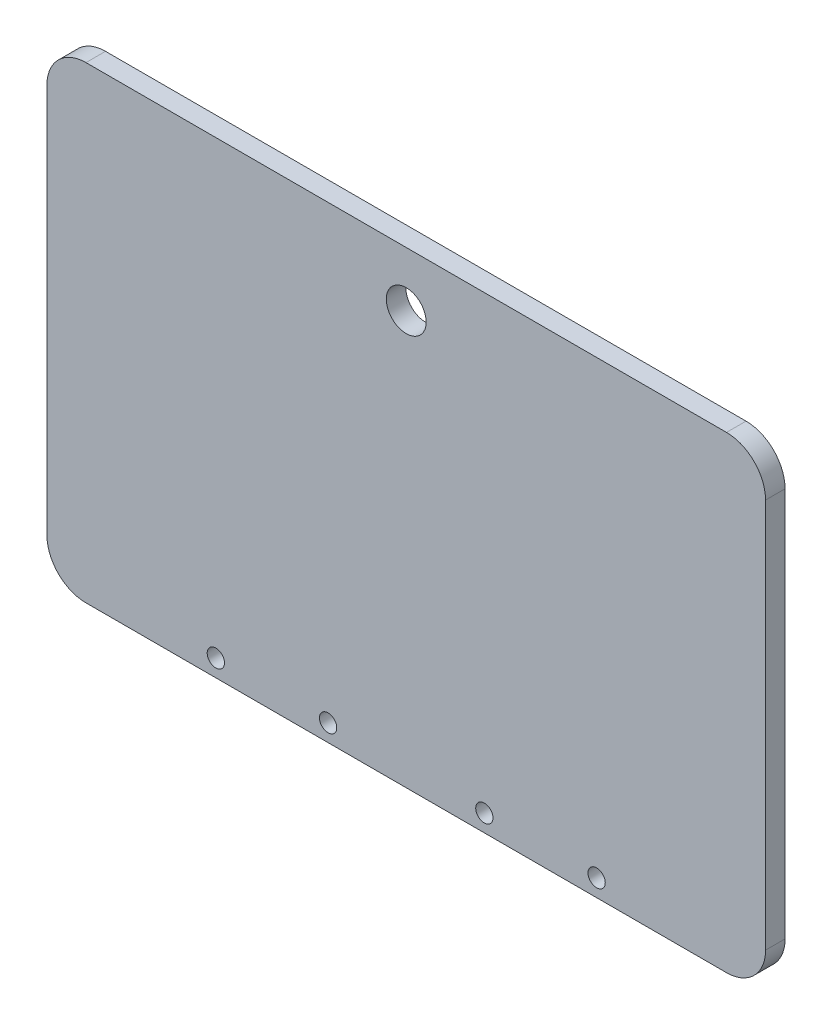
SolidWorks part; units mm, degrees
material "Acrylic (Medium-high impact)"
ref_plane "Front Plane" through (0, 0, 0) normal (0, 0, 1) x (1, 0, 0)
ref_plane "Top Plane" through (0, 0, 0) normal (0, 1, 0) x (1, 0, 0)
ref_plane "Right Plane" through (0, 0, 0) normal (1, 0, 0) x (0, 0, -1)
sketch "Sketch1" plane through (0, 0, 0) normal (0, 0, 1) x (1, 0, 0)
  line L1 (233.68, 152.146) -> (0, 152.146)
  line L2 (233.68, 152.146) -> (233.68, 0)
  line L3 (233.68, 0) -> (0, 0)
  line L4 (0, 152.146) -> (0, 0)
  line L5 (233.68, 152.146) -> (0, 0) construction
  line L6 (233.68, 0) -> (0, 152.146) construction
  point P0 (116.84, 76.073)
  dimension "D1" = 152.146
  dimension "D2" = 233.68
extrude "Boss-Extrude1" add sketch "Sketch1" along normal blind 6.35
hole_wizard "#10 Clearance Hole1" positions "Sketch6" profile "Sketch7" hole size "#10" standard "ANSI Inch" end condition through all
sketch "Sketch6" plane through (0, 0, 6.35) normal (0, 0, 1) x (1, 0, 0)
  line L2 (0, 0) -> (233.68, 0) construction
  line L3 (91.44, 5.588) -> (142.24, 5.588) construction
  line L5 (116.84, 0) -> (116.84, 5.588) construction
  line L6 (54.9275, 5.588) -> (91.44, 5.588) construction
  line L9 (142.24, 5.588) -> (178.7525, 5.588) construction
  point P0 (54.9275, 5.588)
  point P11 (91.44, 5.588)
  point P13 (142.24, 5.588)
  point P15 (178.7525, 5.588)
  dimension "D1" = 36.5125
  dimension "D2" = 5.588
  dimension "D5" = 50.8
sketch "Sketch7" plane through (54.9275, 5.588, 6.35) normal (1, 0, 0) x (0, -1, 0)
  line L0 (0, 0) -> (0, 6.35)
  line L1 (0, 6.35) -> (2.8067, 6.35)
  line L2 (2.8067, 6.35) -> (2.8067, 0)
  line L5 (2.8067, 0) -> (0, 0)
  line L11 (0, -6.35) -> (0, 107.95) construction
  dimension "Thru Hole Dia." = 5.6134
  dimension "Thru Hole Depth" = 6.35
sketch "Sketch8" plane through (0, 0, 6.35) normal (0, 0, 1) x (1, 0, 0)
  line L0 (0, 0) -> (233.68, 0) construction
  line L1 (233.68, 152.146) -> (0, 152.146) construction
  circle A0 centre (116.84, 134.366) radius 6.477
  point P6 (116.84, 0)
  dimension "D1" = 12.954
  dimension "D2" = 17.78
extrude "Cut-Extrude1" cut sketch "Sketch8" against normal through all
fillet "Fillet1" radius 12.7 4 edges at (233.68, 0, 3.175) (233.68, 152.146, 3.175) (0, 152.146, 3.175) (0, 0, 3.175)
